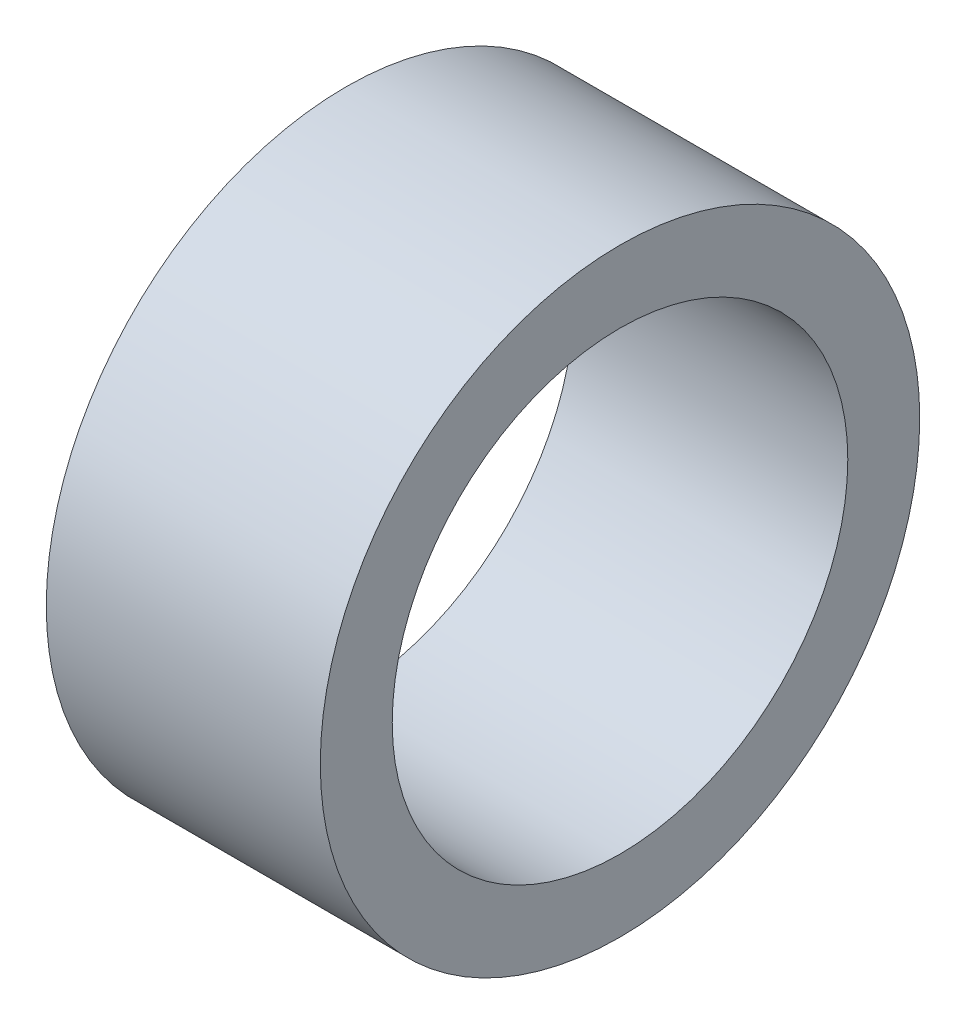
SolidWorks part; units mm, degrees
material "Nylon 6/10"
ref_plane "Front Plane" through (0, 0, 0) normal (0, 0, 1) x (1, 0, 0)
ref_plane "Top Plane" through (0, 0, 0) normal (0, 1, 0) x (1, 0, 0)
ref_plane "Right Plane" through (0, 0, 0) normal (1, 0, 0) x (0, 0, -1)
sketch "Sketch1" plane through (0, 0, 0) normal (0, 0, 1) x (1, 0, 0)
  line L0 (38.1, -13.8602) -> (38.1, 12.314) construction
  line L1 (38.1, 5.5563) -> (43.18, 5.5563)
  line L2 (38.1, 5.5563) -> (38.1, 4.2228)
  line L3 (38.1, 4.2228) -> (43.18, 4.2228)
  line L4 (43.18, 5.5563) -> (43.18, 4.2228)
  line L5 (0, 0) -> (42.6651, 0) construction
  line L7 (44.1854, 3.9688) -> (-54.7878, 3.9688) construction
  dimension "D1" = 0.254
  dimension "D2" = 11.1125
  dimension "D3" = 5.08
revolve "Revolve1" add sketch "Sketch1" angle 360 about L5
